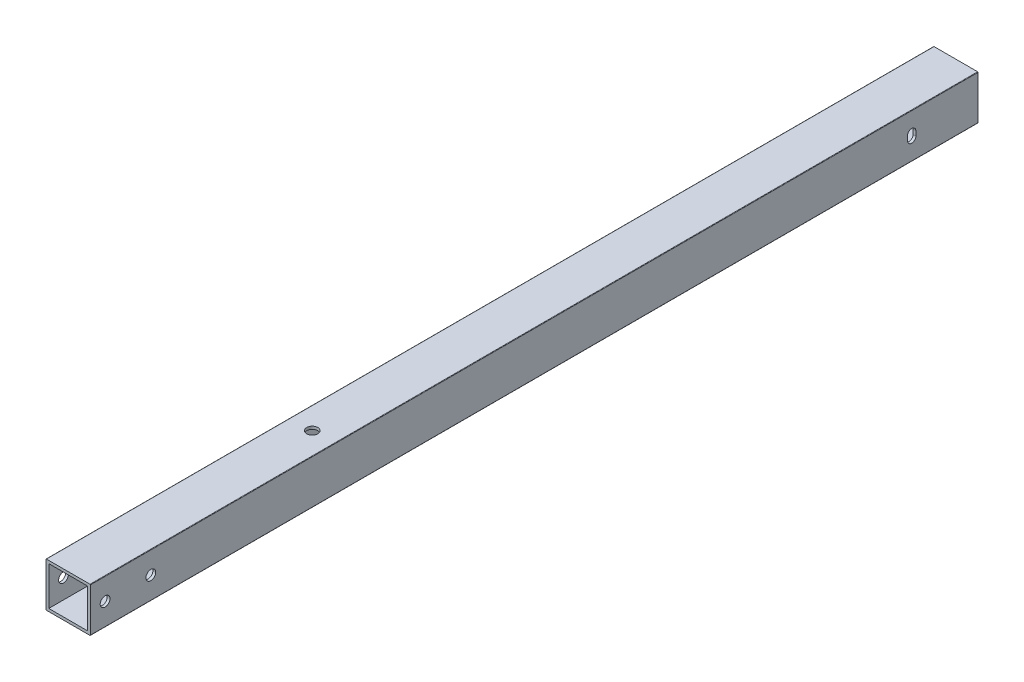
SolidWorks part; units mm, degrees
material "1060 Alloy"
ref_plane "Front Plane" through (0, 0, 0) normal (0, 0, 1) x (1, 0, 0)
ref_plane "Top Plane" through (0, 0, 0) normal (0, 1, 0) x (1, 0, 0)
ref_plane "Right Plane" through (0, 0, 0) normal (1, 0, 0) x (0, 0, -1)
ref_plane "Plane1" through (0, 0, 0) normal (0, 0, -1) x (-1, 0, 0)
sketch "Sketch1" plane through (0, 0, 0) normal (0, 0, -1) x (-1, 0, 0)
  line L4 (1.5875, -1.3335) -> (1.5875, 23.5585)
  line L5 (1.3335, 23.8125) -> (-23.5585, 23.8125)
  line L6 (-23.8125, 23.5585) -> (-23.8125, -1.3335)
  line L7 (-23.5585, -1.5875) -> (1.3335, -1.5875)
  line L9 (0, 22.225) -> (-22.225, 22.225)
  line L10 (0, 22.225) -> (0, 0)
  line L11 (0, 0) -> (-22.225, 0)
  line L12 (-22.225, 22.225) -> (-22.225, 0)
  line L13 (0, 22.225) -> (-22.225, 0) construction
  line L14 (0, 0) -> (-22.225, 22.225) construction
  arc A4 (1.3335, -1.5875) -> (1.5875, -1.3335) centre (1.3335, -1.3335) ccw
  arc A5 (1.5875, 23.5585) -> (1.3335, 23.8125) centre (1.3335, 23.5585) ccw
  arc A6 (-23.5585, 23.8125) -> (-23.8125, 23.5585) centre (-23.5585, 23.5585) ccw
  arc A7 (-23.8125, -1.3335) -> (-23.5585, -1.5875) centre (-23.5585, -1.3335) ccw
  point P24 (-11.1125, 11.1125)
  dimension "D1" = 25.4
  dimension "D2" = 25.4
  dimension "D3" = 1.5875
  dimension "D4" = 1.5875
  dimension "D5" = 1.5875
extrude "Boss-Extrude1" add sketch "Sketch1" against normal blind 508
sketch "Sketch2" plane through (-1.5875, 0, 0) normal (-1, 0, 0) x (0, 0, 1)
  line L0 (0, -1.3335) -> (0, 23.5585) construction
  line L1 (508, -1.3335) -> (0, -1.3335) construction
  line L2 (508, -1.3335) -> (508, 23.5585) construction
  circle A0 centre (12.6975, 11.3665) radius 1.5875
  circle A1 centre (495.3, 11.3665) radius 1.5875
  circle A2 centre (76.2, 11.3665) radius 6.35
  circle A3 centre (431.8, 11.3665) radius 6.35
  point P4 (0, 11.1125)
  dimension "D1" = 3.175
  dimension "D2" = 12.7
  dimension "D3" = 12.7
  dimension "D4" = 3.175
  dimension "D5" = 12.7
  dimension "D6" = 12.7
  dimension "D7" = 12.7
  dimension "D8" = 12.7
  dimension "D9" = 76.2
  dimension "D10" = 12.7
  dimension "D11" = 12.7
  dimension "D12" = 76.2
extrude "Cut-Extrude1" [suppressed] cut sketch "Sketch2" against normal through all
sketch "Sketch4" plane through (23.8125, 0, 0) normal (1, 0, 0) x (0, 0, -1)
  line L2 (-40.3145, 9.8425) -> (-40.3145, 12.3825)
  line L4 (-35.552, 9.8425) -> (-35.552, 12.3825)
  line L6 (-40.3145, 12.3825) -> (-35.552, 12.3825)
  line L7 (-40.3145, 11.1125) -> (-35.552, 11.1125)
  line L8 (0, 23.5585) -> (0, -1.3335) construction
  line L9 (0, 11.1125) -> (-49.6378, 11.1125)
  circle A0 centre (-37.9333, 9.8425) radius 2.3812
  circle A1 centre (-37.9333, 12.3825) radius 2.3812
  dimension "D1" = 4.7625
  dimension "D2" = 37.9333
  dimension "D3" = 1.27
extrude "Cut-Extrude2" cut sketch "Sketch4" against normal through all contours L6 A1 | L6 A1 A0 | L9 A0 | L9 A1 | A1 A0 | A0 L4 L7 | A1 L7 L4 | A0 L7 L2 | A1 L2 L7 | A0 region at (23.8125, 9.1445, 37.9333) region at (23.8125, 10.8001, 40.2061) region at (23.8125, 11.4249, 40.2061) region at (23.8125, 10.8001, 35.6605) region at (23.8125, 11.5673, 37.9333) region at (23.8125, 11.7352, 40.1736) region at (23.8125, 10.6577, 37.9333) region at (23.8125, 13.3931, 37.9333) region at (23.8125, 11.4249, 35.6605)
sketch "Sketch5" plane through (23.8125, 0, 0) normal (1, 0, 0) x (0, 0, -1)
  circle A0 centre (-499.5773, 11.171) radius 2.794
  circle A1 centre (-473.4153, 11.171) radius 2.794
extrude "Cut-Extrude3" cut sketch "Sketch5" against normal blind 25.4
sketch "Sketch6" plane through (0, -1.5875, 0) normal (0, -1, 0) x (1, 0, 0)
  line L0 (11.1125, 508) -> (11.1125, 368.3) construction
  line L1 (23.5585, 508) -> (-1.3335, 508) construction
  circle A0 centre (11.1125, 368.3) radius 3.175
  dimension "D2" = 6.35
  dimension "D1" = 139.7
extrude "Cut-Extrude4" cut sketch "Sketch6" against normal through all
